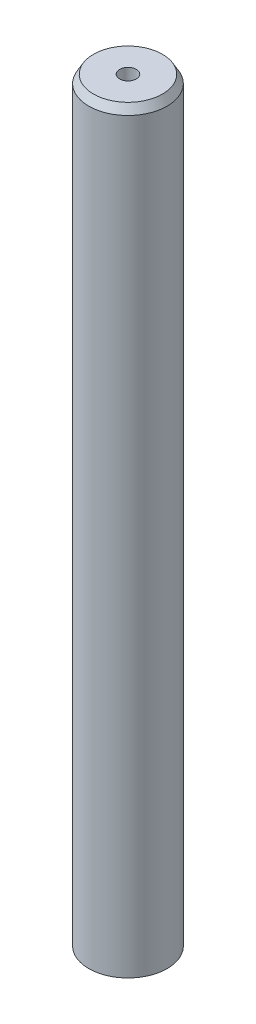
SolidWorks part; units mm, degrees
ref_plane "Front Plane" through (0, 0, 0) normal (0, 0, 1) x (1, 0, 0)
ref_plane "Top Plane" through (0, 0, 0) normal (0, 1, 0) x (1, 0, 0)
ref_plane "Right Plane" through (0, 0, 0) normal (1, 0, 0) x (0, 0, -1)
sketch "Sketch1" plane through (0, 0, 0) normal (0, 1, 0) x (1, 0, 0)
  circle A0 centre (0, 0) radius 5
  dimension "SHAFT_OD" = 10
extrude "Boss-Extrude1" add sketch "Sketch1" along normal blind 96.9529
sketch "Sketch2" plane through (0, 0, 0) normal (0, 1, 0) x (1, 0, 0)
  circle A0 centre (0, 0) radius 1.0644
  dimension "BORE_D" = 2.1288
extrude "Cut-Extrude1" cut sketch "Sketch2" along normal through all
chamfer "Chamfer1" distance 1.036 angle 30 2 edges at (0, 96.9529, 5) (0, 0, 5) first distance on face at (0, 96.9529, 5) first distance on face at (0, 0, 1.0644)
